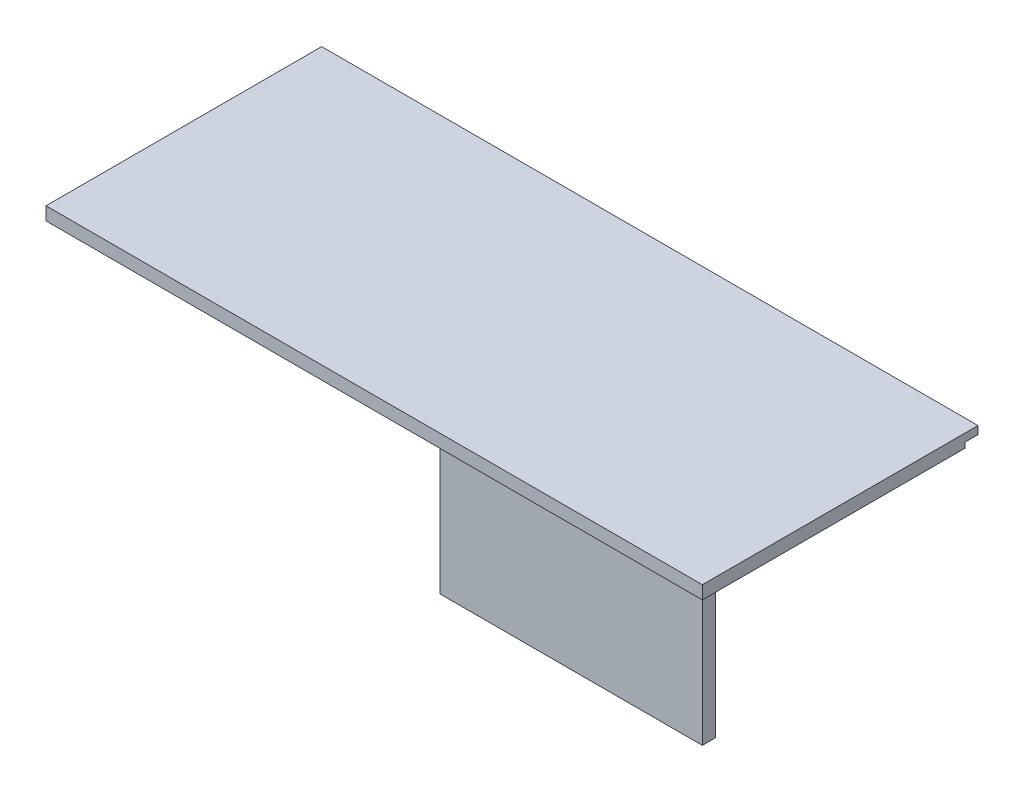
SolidWorks part; units mm, degrees
ref_plane "Front Plane" through (0, 0, 0) normal (0, 0, 1) x (1, 0, 0)
ref_plane "Top Plane" through (0, 0, 0) normal (0, 1, 0) x (1, 0, 0)
ref_plane "Right Plane" through (0, 0, 0) normal (1, 0, 0) x (0, 0, -1)
sketch "Sketch1" plane through (0, 0, 0) normal (1, 0, 0) x (0, 0, -1)
  line L0 (-100, 0) -> (0, 0)
  line L1 (0, 0) -> (0, 2)
  line L2 (0, 2) -> (5, 2)
  line L3 (5, 2) -> (5, 5)
  line L4 (5, 5) -> (-100, 5)
  line L5 (-100, 5) -> (-100, 0)
  line L6 (-35, 0) -> (-35, -10)
  line L7 (0, 2) -> (5, 2)
  line L8 (0, 2) -> (0, -148)
  line L9 (0, -148) -> (5, -148)
  line L10 (5, 2) -> (5, -148)
  line L11 (-35, -10) -> (-10, -10)
  line L12 (-10, -10) -> (-10, -35)
  line L13 (-10, -35) -> (0, -35)
  line L14 (0, -35) -> (0, 0)
  line L15 (0, 0) -> (-35, 0)
  dimension "D1" = 5
  dimension "D2" = 100
  dimension "D3" = 5
  dimension "D4" = 2
  dimension "D5" = 150
  dimension "D6" = 10
  dimension "D7" = 0
  dimension "D8" = 0
  dimension "D9" = 25
sketch "Sketch2" plane through (0, 0, 0) normal (1, 0, 0) x (0, 0, -1)
  line L0 (0, 0) -> (0, 2) construction
  line L1 (-100, 0) -> (0, 0) construction
  line L2 (-100, 5) -> (-100, 0) construction
  line L3 (5, 5) -> (-100, 5) construction
  line L4 (5, 2) -> (5, 5) construction
  line L5 (0, 2) -> (5, 2) construction
  line L6 (0, 2) -> (5, 2) construction
  line L7 (5, 2) -> (5, -148) construction
  line L8 (0, -148) -> (5, -148) construction
  line L9 (0, 2) -> (0, -148) construction
  line L10 (0, 0) -> (0, 2)
  line L11 (-100, 0) -> (0, 0)
  line L12 (-100, 5) -> (-100, 0)
  line L13 (5, 5) -> (-100, 5)
  line L14 (5, 2) -> (5, 5)
  line L15 (0, 2) -> (5, 2)
  line L16 (0, 2) -> (5, 2)
  line L17 (5, 2) -> (5, -148)
  line L18 (0, -148) -> (5, -148)
  line L19 (0, 2) -> (0, -148)
  line L20 (-10, -35) -> (0, -35) construction
  line L21 (0, -35) -> (0, 0) construction
  line L22 (0, 0) -> (-35, 0) construction
  line L23 (-35, 0) -> (-35, -10) construction
  line L24 (-35, -10) -> (-10, -10) construction
  line L25 (-10, -10) -> (-10, -35) construction
  line L26 (-10, -35) -> (0, -35)
  line L27 (0, -35) -> (0, 0)
  line L28 (0, 0) -> (-35, 0)
  line L29 (-35, 0) -> (-35, -10)
  line L30 (-35, -10) -> (-10, -10)
  line L31 (-10, -10) -> (-10, -35)
extrude "Boss-Extrude3" add sketch "Sketch2" along normal blind 150 and the other way blind 100 contours L10 L15 L14 L13 L12 L11 region at (0, 2.5291, 48.4709)
extrude "Boss-Extrude4" add sketch "Sketch2<3>" along normal mid plane 100 separate body contours L10 L19 L18 L17 L15 region at (0, -73, -2.5)
sketch "Sketch2<3>" plane through (0, 0, 0) normal (1, 0, 0) x (0, 0, -1) same geometry as "Sketch2"
